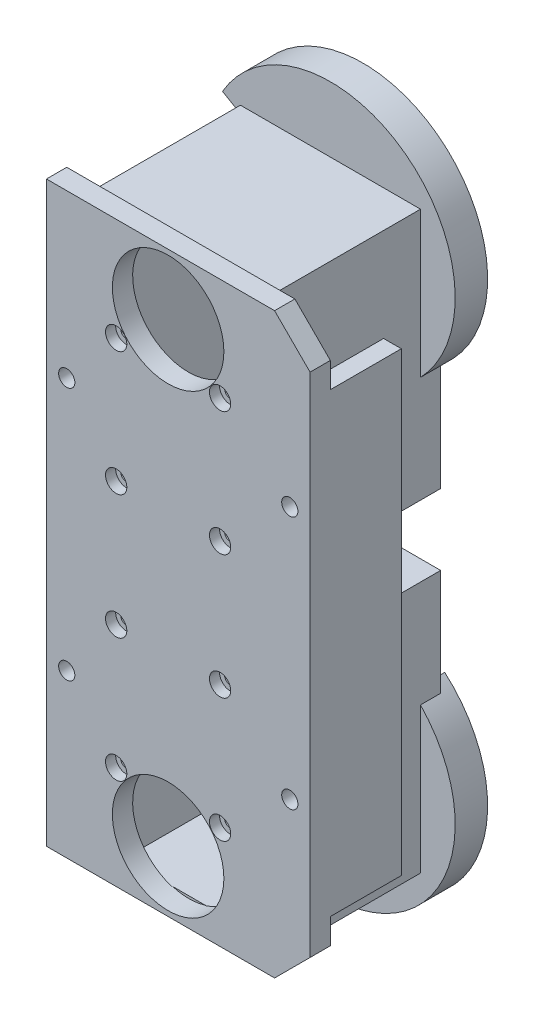
SolidWorks part; units mm, degrees
ref_plane "Front Plane" through (0, 0, 0) normal (0, 0, 1) x (1, 0, 0)
ref_plane "Top Plane" through (0, 0, 0) normal (0, 1, 0) x (1, 0, 0)
ref_plane "Right Plane" through (0, 0, 0) normal (1, 0, 0) x (0, 0, -1)
ref_plane "PZ_p64_625" through (0, 0, 64.625) normal (0, 0, 1) x (1, 0, 0)
sketch "S_prism1" plane through (0, 0, 64.625) normal (0, 0, 1) x (1, 0, 0)
  line L0 (28, -50) -> (28, 50)
  line L1 (28, 50) -> (21, 57)
  line L2 (21, 57) -> (-24, 57)
  line L3 (-24, 57) -> (-24, -57)
  line L4 (-24, -57) -> (21, -57)
  line L5 (21, -57) -> (28, -50)
extrude "Boss_1" add sketch "S_prism1" along normal blind 4
ref_plane "PZ_p50_625" through (0, 0, 50.625) normal (0, 0, 1) x (1, 0, 0)
sketch "S_box2" plane through (0, 0, 50.625) normal (0, 0, 1) x (1, 0, 0)
  line L0 (24.5, -45) -> (28, -45)
  line L1 (28, -45) -> (28, 45)
  line L2 (28, 45) -> (24.5, 45)
  line L3 (24.5, 45) -> (24.5, -45)
  dimension "P1" = 24.5
  dimension "P2" = 45
  dimension "P3" = 28
  dimension "P4" = 45
  dimension "P5" = 28
  dimension "P6" = 45
  dimension "P7" = 24.5
  dimension "P8" = 45
extrude "Boss_2" add sketch "S_box2" along normal blind 14.5
sketch "S_box3" plane through (0, 0, 50.625) normal (0, 0, 1) x (1, 0, 0)
  line L0 (-24, -45) -> (-20.5, -45)
  line L1 (-20.5, -45) -> (-20.5, 45)
  line L2 (-20.5, 45) -> (-24, 45)
  line L3 (-24, 45) -> (-24, -45)
  dimension "P1" = 24
  dimension "P2" = 45
  dimension "P3" = 20.5
  dimension "P4" = 45
  dimension "P5" = 20.5
  dimension "P6" = 45
  dimension "P7" = 24
  dimension "P8" = 45
extrude "Boss_3" add sketch "S_box3" along normal blind 14.5
ref_plane "PZ_p32_625" through (0, 0, 32.625) normal (0, 0, 1) x (1, 0, 0)
sketch "S_box4" plane through (0, 0, 32.625) normal (0, 0, 1) x (1, 0, 0)
  line L0 (-17.76, 6.99) -> (17.76, 6.99)
  line L1 (17.76, 6.99) -> (17.76, 9.49)
  line L2 (17.76, 9.49) -> (-17.76, 9.49)
  line L3 (-17.76, 9.49) -> (-17.76, 6.99)
  dimension "P1" = 17.76
  dimension "P2" = 6.99
  dimension "P3" = 17.76
  dimension "P4" = 6.99
  dimension "P5" = 17.76
  dimension "P6" = 9.49
  dimension "P7" = 17.76
  dimension "P8" = 9.49
extrude "Boss_4" add sketch "S_box4" along normal blind 36
sketch "S_box5" plane through (0, 0, 32.625) normal (0, 0, 1) x (1, 0, 0)
  line L0 (-17.76, 55.51) -> (17.76, 55.51)
  line L1 (17.76, 55.51) -> (17.76, 56.71)
  line L2 (17.76, 56.71) -> (-17.76, 56.71)
  line L3 (-17.76, 56.71) -> (-17.76, 55.51)
  dimension "P1" = 17.76
  dimension "P2" = 55.51
  dimension "P3" = 17.76
  dimension "P4" = 55.51
  dimension "P5" = 17.76
  dimension "P6" = 56.71
  dimension "P7" = 17.76
  dimension "P8" = 56.71
extrude "Boss_5" add sketch "S_box5" along normal blind 36
sketch "S_box6" plane through (0, 0, 32.625) normal (0, 0, 1) x (1, 0, 0)
  line L0 (-17.76, 6.99) -> (-12.76, 6.99)
  line L1 (-12.76, 6.99) -> (-12.76, 56.71)
  line L2 (-12.76, 56.71) -> (-17.76, 56.71)
  line L3 (-17.76, 56.71) -> (-17.76, 6.99)
  dimension "P1" = 17.76
  dimension "P2" = 6.99
  dimension "P3" = 12.76
  dimension "P4" = 6.99
  dimension "P5" = 12.76
  dimension "P6" = 56.71
  dimension "P7" = 17.76
  dimension "P8" = 56.71
extrude "Boss_6" add sketch "S_box6" along normal blind 36
sketch "S_box7" plane through (0, 0, 32.625) normal (0, 0, 1) x (1, 0, 0)
  line L0 (12.76, 6.99) -> (17.76, 6.99)
  line L1 (17.76, 6.99) -> (17.76, 56.71)
  line L2 (17.76, 56.71) -> (12.76, 56.71)
  line L3 (12.76, 56.71) -> (12.76, 6.99)
  dimension "P1" = 12.76
  dimension "P2" = 6.99
  dimension "P3" = 17.76
  dimension "P4" = 6.99
  dimension "P5" = 17.76
  dimension "P6" = 56.71
  dimension "P7" = 12.76
  dimension "P8" = 56.71
extrude "Boss_7" add sketch "S_box7" along normal blind 36
sketch "S_box8" plane through (0, 0, 64.625) normal (0, 0, 1) x (1, 0, 0)
  line L0 (-17.76, 6.99) -> (17.76, 6.99)
  line L1 (17.76, 6.99) -> (17.76, 56.71)
  line L2 (17.76, 56.71) -> (-17.76, 56.71)
  line L3 (-17.76, 56.71) -> (-17.76, 6.99)
  dimension "P1" = 17.76
  dimension "P2" = 6.99
  dimension "P3" = 17.76
  dimension "P4" = 6.99
  dimension "P5" = 17.76
  dimension "P6" = 56.71
  dimension "P7" = 17.76
  dimension "P8" = 56.71
extrude "Boss_8" add sketch "S_box8" along normal blind 4
ref_plane "PZ_p30_100" through (0, 0, 30.1) normal (0, 0, 1) x (1, 0, 0)
sketch "S_cyl9" plane through (0, 0, 30.1) normal (0, 0, 1) x (1, 0, 0)
  circle A0 centre (0, 45) radius 19
  dimension "D1_S_cyl9" = 38
  dimension "P2" = 45
extrude "Boss_9" add sketch "S_cyl9" along normal blind 2.525
ref_plane "PZ_p30_200" through (0, 0, 30.2) normal (0, 0, 1) x (1, 0, 0)
sketch "S_prism10" plane through (0, 0, 30.2) normal (0, 0, 1) x (1, 0, 0)
  line L0 (-21.3042, 57.3) -> (-9.5263, 50.5)
  line L1 (7.2166, 36.6982) -> (16.1391, 26.4341)
  arc A0 (16.1391, 26.4341) -> (-21.3042, 57.3) centre (0, 45) ccw
  arc A1 (-9.5263, 50.5) -> (7.2166, 36.6982) centre (0, 45) cw
extrude "Boss_10" add sketch "S_prism10" along normal blind 6.4
sketch "S_box11" plane through (0, 0, 32.625) normal (0, 0, 1) x (1, 0, 0)
  line L0 (-17.76, -56.71) -> (17.76, -56.71)
  line L1 (17.76, -56.71) -> (17.76, -55.51)
  line L2 (17.76, -55.51) -> (-17.76, -55.51)
  line L3 (-17.76, -55.51) -> (-17.76, -56.71)
  dimension "P1" = 17.76
  dimension "P2" = 56.71
  dimension "P3" = 17.76
  dimension "P4" = 56.71
  dimension "P5" = 17.76
  dimension "P6" = 55.51
  dimension "P7" = 17.76
  dimension "P8" = 55.51
extrude "Boss_11" add sketch "S_box11" along normal blind 36
sketch "S_box12" plane through (0, 0, 32.625) normal (0, 0, 1) x (1, 0, 0)
  line L0 (-17.76, -9.49) -> (17.76, -9.49)
  line L1 (17.76, -9.49) -> (17.76, -6.99)
  line L2 (17.76, -6.99) -> (-17.76, -6.99)
  line L3 (-17.76, -6.99) -> (-17.76, -9.49)
  dimension "P1" = 17.76
  dimension "P2" = 9.49
  dimension "P3" = 17.76
  dimension "P4" = 9.49
  dimension "P5" = 17.76
  dimension "P6" = 6.99
  dimension "P7" = 17.76
  dimension "P8" = 6.99
extrude "Boss_12" add sketch "S_box12" along normal blind 36
sketch "S_box13" plane through (0, 0, 32.625) normal (0, 0, 1) x (1, 0, 0)
  line L0 (-17.76, -56.71) -> (-12.76, -56.71)
  line L1 (-12.76, -56.71) -> (-12.76, -6.99)
  line L2 (-12.76, -6.99) -> (-17.76, -6.99)
  line L3 (-17.76, -6.99) -> (-17.76, -56.71)
  dimension "P1" = 17.76
  dimension "P2" = 56.71
  dimension "P3" = 12.76
  dimension "P4" = 56.71
  dimension "P5" = 12.76
  dimension "P6" = 6.99
  dimension "P7" = 17.76
  dimension "P8" = 6.99
extrude "Boss_13" add sketch "S_box13" along normal blind 36
sketch "S_box14" plane through (0, 0, 32.625) normal (0, 0, 1) x (1, 0, 0)
  line L0 (12.76, -56.71) -> (17.76, -56.71)
  line L1 (17.76, -56.71) -> (17.76, -6.99)
  line L2 (17.76, -6.99) -> (12.76, -6.99)
  line L3 (12.76, -6.99) -> (12.76, -56.71)
  dimension "P1" = 12.76
  dimension "P2" = 56.71
  dimension "P3" = 17.76
  dimension "P4" = 56.71
  dimension "P5" = 17.76
  dimension "P6" = 6.99
  dimension "P7" = 12.76
  dimension "P8" = 6.99
extrude "Boss_14" add sketch "S_box14" along normal blind 36
sketch "S_box15" plane through (0, 0, 64.625) normal (0, 0, 1) x (1, 0, 0)
  line L0 (-17.76, -56.71) -> (17.76, -56.71)
  line L1 (17.76, -56.71) -> (17.76, -6.99)
  line L2 (17.76, -6.99) -> (-17.76, -6.99)
  line L3 (-17.76, -6.99) -> (-17.76, -56.71)
  dimension "P1" = 17.76
  dimension "P2" = 56.71
  dimension "P3" = 17.76
  dimension "P4" = 56.71
  dimension "P5" = 17.76
  dimension "P6" = 6.99
  dimension "P7" = 17.76
  dimension "P8" = 6.99
extrude "Boss_15" add sketch "S_box15" along normal blind 4
sketch "S_cyl16" plane through (0, 0, 30.1) normal (0, 0, 1) x (1, 0, 0)
  circle A0 centre (0, -45) radius 19
  dimension "D1_S_cyl16" = 38
  dimension "P2" = 45
extrude "Boss_16" add sketch "S_cyl16" along normal blind 2.525
sketch "S_prism17" plane through (0, 0, 30.2) normal (0, 0, 1) x (1, 0, 0)
  line L0 (16.1391, -26.4341) -> (7.2166, -36.6982)
  line L1 (-9.5263, -50.5) -> (-21.3042, -57.3)
  arc A0 (-21.3042, -57.3) -> (16.1391, -26.4341) centre (0, -45) ccw
  arc A1 (7.2166, -36.6982) -> (-9.5263, -50.5) centre (0, -45) cw
extrude "Boss_17" add sketch "S_prism17" along normal blind 6.4
ref_plane "PZ_p64_525" through (0, 0, 64.525) normal (0, 0, 1) x (1, 0, 0)
sketch "S_hole18" plane through (0, 0, 64.525) normal (0, 0, 1) x (1, 0, 0)
  circle A0 centre (0, 45) radius 11
  dimension "D1_S_hole18" = 22
  dimension "P2" = 45
extrude "Hole_18" cut sketch "S_hole18" along normal blind 4.2
sketch "S_hole19" plane through (0, 0, 64.525) normal (0, 0, 1) x (1, 0, 0)
  circle A0 centre (-10.25, 36.7) radius 1.1
  dimension "D1_S_hole19" = 2.2
  dimension "P2" = 10.25
  dimension "P3" = 36.7
extrude "Hole_19" cut sketch "S_hole19" along normal blind 4.2
ref_plane "PZ_p66_625" through (0, 0, 66.625) normal (0, 0, 1) x (1, 0, 0)
sketch "S_hole20" plane through (0, 0, 66.625) normal (0, 0, 1) x (1, 0, 0)
  circle A0 centre (-10.25, 36.7) radius 2.1
  dimension "D1_S_hole20" = 4.2
  dimension "P2" = 10.25
  dimension "P3" = 36.7
extrude "Hole_20" cut sketch "S_hole20" along normal blind 2.1
sketch "S_hole21" plane through (0, 0, 64.525) normal (0, 0, 1) x (1, 0, 0)
  circle A0 centre (10.25, 36.7) radius 1.1
  dimension "D1_S_hole21" = 2.2
  dimension "P2" = 10.25
  dimension "P3" = 36.7
extrude "Hole_21" cut sketch "S_hole21" along normal blind 4.2
sketch "S_hole22" plane through (0, 0, 66.625) normal (0, 0, 1) x (1, 0, 0)
  circle A0 centre (10.25, 36.7) radius 2.1
  dimension "D1_S_hole22" = 4.2
  dimension "P2" = 10.25
  dimension "P3" = 36.7
extrude "Hole_22" cut sketch "S_hole22" along normal blind 2.1
sketch "S_hole23" plane through (0, 0, 64.525) normal (0, 0, 1) x (1, 0, 0)
  circle A0 centre (-10.25, 12.25) radius 1.1
  dimension "D1_S_hole23" = 2.2
  dimension "P2" = 10.25
  dimension "P3" = 12.25
extrude "Hole_23" cut sketch "S_hole23" along normal blind 4.2
sketch "S_hole24" plane through (0, 0, 66.625) normal (0, 0, 1) x (1, 0, 0)
  circle A0 centre (-10.25, 12.25) radius 2.1
  dimension "D1_S_hole24" = 4.2
  dimension "P2" = 10.25
  dimension "P3" = 12.25
extrude "Hole_24" cut sketch "S_hole24" along normal blind 2.1
sketch "S_hole25" plane through (0, 0, 64.525) normal (0, 0, 1) x (1, 0, 0)
  circle A0 centre (10.25, 12.25) radius 1.1
  dimension "D1_S_hole25" = 2.2
  dimension "P2" = 10.25
  dimension "P3" = 12.25
extrude "Hole_25" cut sketch "S_hole25" along normal blind 4.2
sketch "S_hole26" plane through (0, 0, 66.625) normal (0, 0, 1) x (1, 0, 0)
  circle A0 centre (10.25, 12.25) radius 2.1
  dimension "D1_S_hole26" = 4.2
  dimension "P2" = 10.25
  dimension "P3" = 12.25
extrude "Hole_26" cut sketch "S_hole26" along normal blind 2.1
sketch "S_cut27" plane through (0, 0, 32.625) normal (0, 0, 1) x (1, 0, 0)
  line L0 (-12.76, 9.49) -> (12.76, 9.49)
  line L1 (12.76, 9.49) -> (12.76, 55.51)
  line L2 (12.76, 55.51) -> (-12.76, 55.51)
  line L3 (-12.76, 55.51) -> (-12.76, 9.49)
  dimension "P1" = 12.76
  dimension "P2" = 9.49
  dimension "P3" = 12.76
  dimension "P4" = 9.49
  dimension "P5" = 12.76
  dimension "P6" = 55.51
  dimension "P7" = 12.76
  dimension "P8" = 55.51
extrude "Pocket_27" cut sketch "S_cut27" along normal blind 4.075
sketch "S_hole28" plane through (0, 0, 30.1) normal (0, 0, 1) x (1, 0, 0)
  circle A0 centre (0, 45) radius 11.5
  dimension "D1_S_hole28" = 23
  dimension "P2" = 45
extrude "Hole_28" cut sketch "S_hole28" along normal blind 2.625
sketch "S_hole29" plane through (0, 0, 30.1) normal (0, 0, 1) x (1, 0, 0)
  circle A0 centre (19.9388, 35.7024) radius 0.9
  dimension "D1_S_hole29" = 1.8
  dimension "P2" = 19.9388
  dimension "P3" = 35.7024
extrude "Hole_29" cut sketch "S_hole29" along normal blind 5.7
sketch "S_hole30" plane through (0, 0, 30.1) normal (0, 0, 1) x (1, 0, 0)
  circle A0 centre (21.2504, 50.694) radius 0.9
  dimension "D1_S_hole30" = 1.8
  dimension "P2" = 21.2504
  dimension "P3" = 50.694
extrude "Hole_30" cut sketch "S_hole30" along normal blind 5.7
sketch "S_hole31" plane through (0, 0, 30.1) normal (0, 0, 1) x (1, 0, 0)
  circle A0 centre (12.6187, 63.0213) radius 0.9
  dimension "D1_S_hole31" = 1.8
  dimension "P2" = 12.6187
  dimension "P3" = 63.0213
extrude "Hole_31" cut sketch "S_hole31" along normal blind 5.7
sketch "S_hole32" plane through (0, 0, 30.1) normal (0, 0, 1) x (1, 0, 0)
  circle A0 centre (0.7678, 66.9866) radius 0.9
  dimension "D1_S_hole32" = 1.8
  dimension "P2" = 0.7678
  dimension "P3" = 66.9866
extrude "Hole_32" cut sketch "S_hole32" along normal blind 5.7
sketch "S_hole33" plane through (0, 0, 64.525) normal (0, 0, 1) x (1, 0, 0)
  circle A0 centre (0, -45) radius 11
  dimension "D1_S_hole33" = 22
  dimension "P2" = 45
extrude "Hole_33" cut sketch "S_hole33" along normal blind 4.2
sketch "S_hole34" plane through (0, 0, 64.525) normal (0, 0, 1) x (1, 0, 0)
  circle A0 centre (-10.25, -36.7) radius 1.1
  dimension "D1_S_hole34" = 2.2
  dimension "P2" = 10.25
  dimension "P3" = 36.7
extrude "Hole_34" cut sketch "S_hole34" along normal blind 4.2
sketch "S_hole35" plane through (0, 0, 66.625) normal (0, 0, 1) x (1, 0, 0)
  circle A0 centre (-10.25, -36.7) radius 2.1
  dimension "D1_S_hole35" = 4.2
  dimension "P2" = 10.25
  dimension "P3" = 36.7
extrude "Hole_35" cut sketch "S_hole35" along normal blind 2.1
sketch "S_hole36" plane through (0, 0, 64.525) normal (0, 0, 1) x (1, 0, 0)
  circle A0 centre (10.25, -36.7) radius 1.1
  dimension "D1_S_hole36" = 2.2
  dimension "P2" = 10.25
  dimension "P3" = 36.7
extrude "Hole_36" cut sketch "S_hole36" along normal blind 4.2
sketch "S_hole37" plane through (0, 0, 66.625) normal (0, 0, 1) x (1, 0, 0)
  circle A0 centre (10.25, -36.7) radius 2.1
  dimension "D1_S_hole37" = 4.2
  dimension "P2" = 10.25
  dimension "P3" = 36.7
extrude "Hole_37" cut sketch "S_hole37" along normal blind 2.1
sketch "S_hole38" plane through (0, 0, 64.525) normal (0, 0, 1) x (1, 0, 0)
  circle A0 centre (-10.25, -12.25) radius 1.1
  dimension "D1_S_hole38" = 2.2
  dimension "P2" = 10.25
  dimension "P3" = 12.25
extrude "Hole_38" cut sketch "S_hole38" along normal blind 4.2
sketch "S_hole39" plane through (0, 0, 66.625) normal (0, 0, 1) x (1, 0, 0)
  circle A0 centre (-10.25, -12.25) radius 2.1
  dimension "D1_S_hole39" = 4.2
  dimension "P2" = 10.25
  dimension "P3" = 12.25
extrude "Hole_39" cut sketch "S_hole39" along normal blind 2.1
sketch "S_hole40" plane through (0, 0, 64.525) normal (0, 0, 1) x (1, 0, 0)
  circle A0 centre (10.25, -12.25) radius 1.1
  dimension "D1_S_hole40" = 2.2
  dimension "P2" = 10.25
  dimension "P3" = 12.25
extrude "Hole_40" cut sketch "S_hole40" along normal blind 4.2
sketch "S_hole41" plane through (0, 0, 66.625) normal (0, 0, 1) x (1, 0, 0)
  circle A0 centre (10.25, -12.25) radius 2.1
  dimension "D1_S_hole41" = 4.2
  dimension "P2" = 10.25
  dimension "P3" = 12.25
extrude "Hole_41" cut sketch "S_hole41" along normal blind 2.1
sketch "S_cut42" plane through (0, 0, 32.625) normal (0, 0, 1) x (1, 0, 0)
  line L0 (-12.76, -55.51) -> (12.76, -55.51)
  line L1 (12.76, -55.51) -> (12.76, -9.49)
  line L2 (12.76, -9.49) -> (-12.76, -9.49)
  line L3 (-12.76, -9.49) -> (-12.76, -55.51)
  dimension "P1" = 12.76
  dimension "P2" = 55.51
  dimension "P3" = 12.76
  dimension "P4" = 55.51
  dimension "P5" = 12.76
  dimension "P6" = 9.49
  dimension "P7" = 12.76
  dimension "P8" = 9.49
extrude "Pocket_42" cut sketch "S_cut42" along normal blind 4.075
sketch "S_hole43" plane through (0, 0, 30.1) normal (0, 0, 1) x (1, 0, 0)
  circle A0 centre (0, -45) radius 11.5
  dimension "D1_S_hole43" = 23
  dimension "P2" = 45
extrude "Hole_43" cut sketch "S_hole43" along normal blind 2.625
sketch "S_hole44" plane through (0, 0, 30.1) normal (0, 0, 1) x (1, 0, 0)
  circle A0 centre (19.9388, -35.7024) radius 0.9
  dimension "D1_S_hole44" = 1.8
  dimension "P2" = 19.9388
  dimension "P3" = 35.7024
extrude "Hole_44" cut sketch "S_hole44" along normal blind 5.7
sketch "S_hole45" plane through (0, 0, 30.1) normal (0, 0, 1) x (1, 0, 0)
  circle A0 centre (21.2504, -50.694) radius 0.9
  dimension "D1_S_hole45" = 1.8
  dimension "P2" = 21.2504
  dimension "P3" = 50.694
extrude "Hole_45" cut sketch "S_hole45" along normal blind 5.7
sketch "S_hole46" plane through (0, 0, 30.1) normal (0, 0, 1) x (1, 0, 0)
  circle A0 centre (12.6187, -63.0213) radius 0.9
  dimension "D1_S_hole46" = 1.8
  dimension "P2" = 12.6187
  dimension "P3" = 63.0213
extrude "Hole_46" cut sketch "S_hole46" along normal blind 5.7
sketch "S_hole47" plane through (0, 0, 30.1) normal (0, 0, 1) x (1, 0, 0)
  circle A0 centre (0.7678, -66.9866) radius 0.9
  dimension "D1_S_hole47" = 1.8
  dimension "P2" = 0.7678
  dimension "P3" = 66.9866
extrude "Hole_47" cut sketch "S_hole47" along normal blind 5.7
sketch "S_hole48" plane through (0, 0, 64.525) normal (0, 0, 1) x (1, 0, 0)
  circle A0 centre (-20, -25) radius 1.6
  dimension "D1_S_hole48" = 3.2
  dimension "P2" = 20
  dimension "P3" = 25
extrude "Hole_48" cut sketch "S_hole48" along normal blind 4.2
sketch "S_hole49" plane through (0, 0, 64.525) normal (0, 0, 1) x (1, 0, 0)
  circle A0 centre (-20, 25) radius 1.6
  dimension "D1_S_hole49" = 3.2
  dimension "P2" = 20
  dimension "P3" = 25
extrude "Hole_49" cut sketch "S_hole49" along normal blind 4.2
sketch "S_hole50" plane through (0, 0, 64.525) normal (0, 0, 1) x (1, 0, 0)
  circle A0 centre (24, -25) radius 1.6
  dimension "D1_S_hole50" = 3.2
  dimension "P2" = 24
  dimension "P3" = 25
extrude "Hole_50" cut sketch "S_hole50" along normal blind 4.2
sketch "S_hole51" plane through (0, 0, 64.525) normal (0, 0, 1) x (1, 0, 0)
  circle A0 centre (24, 25) radius 1.6
  dimension "D1_S_hole51" = 3.2
  dimension "P2" = 24
  dimension "P3" = 25
extrude "Hole_51" cut sketch "S_hole51" along normal blind 4.2
equation "\"plate_t\" = 3"
equation "\"clearance\" = 0.4"
